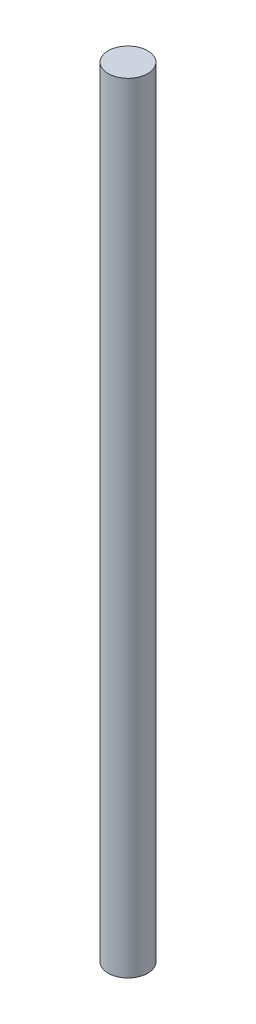
SolidWorks part; units mm, degrees
ref_plane "Front Plane" through (0, 0, 0) normal (0, 0, 1) x (1, 0, 0)
ref_plane "Top Plane" through (0, 0, 0) normal (0, 1, 0) x (1, 0, 0)
ref_plane "Right Plane" through (0, 0, 0) normal (1, 0, 0) x (0, 0, -1)
sketch "Sketch1" plane through (0, 0, 0) normal (0, 1, 0) x (1, 0, 0)
  circle A0 centre (0, 0) radius 12.7
  dimension "D1" = 25.4
extrude "Boss-Extrude1" add sketch "Sketch1" along normal blind 500
equation "\"D1@Sketch1\" = \"cf_tube_outer_diameter\""
equation "\"D1@Boss-Extrude1\"= \"mid_tube_length\""
equation "\"cf_tube_outer_diameter\" = 25.4mm"
equation "\"mid_plate_mid_to_top\" = 100mm"
equation "\"mid_plate_mid_to_bottom\" = 125mm"
equation "\"mid_plate_horizontal_spacing\" = 250mm"
equation "\"mid_tube_length\" = 500mm"
